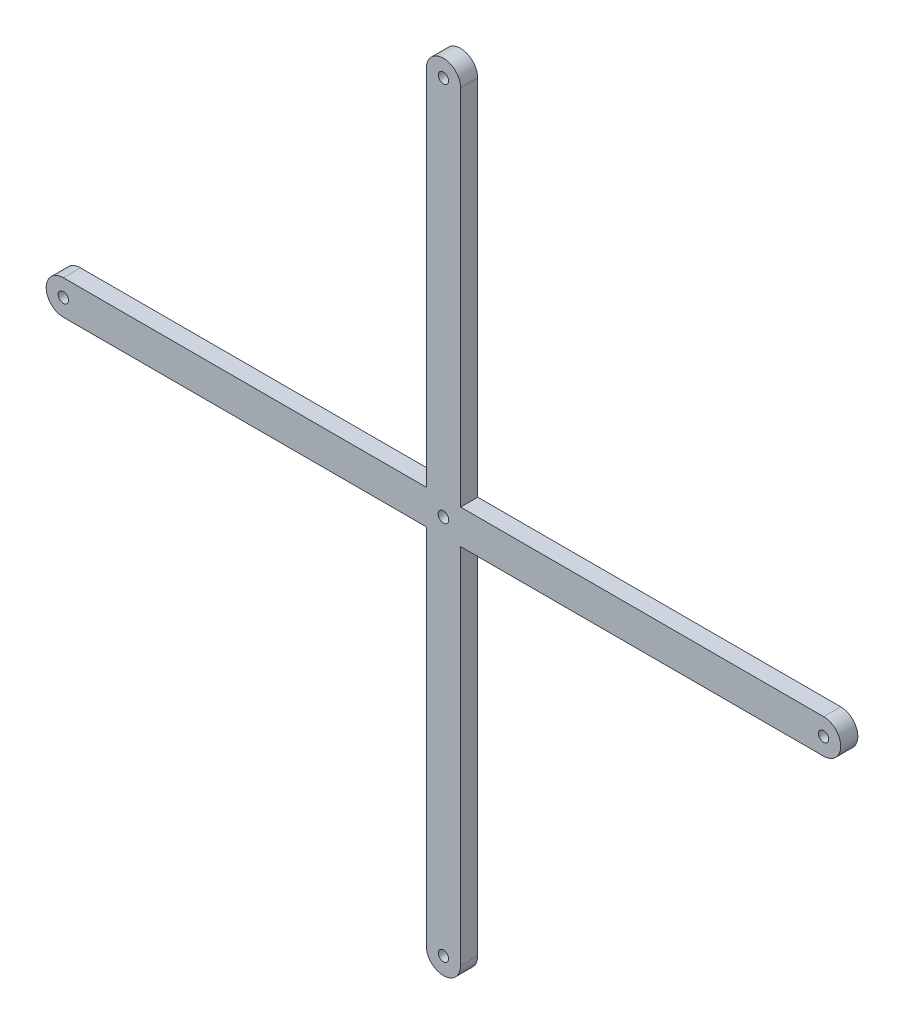
SolidWorks part; units mm, degrees
ref_plane "Front Plane" through (0, 0, 0) normal (0, 0, 1) x (1, 0, 0)
ref_plane "Top Plane" through (0, 0, 0) normal (0, 1, 0) x (1, 0, 0)
ref_plane "Right Plane" through (0, 0, 0) normal (1, 0, 0) x (0, 0, -1)
sketch "Sketch1" plane through (0, 0, 0) normal (0, 0, 1) x (1, 0, 0)
  line L0 (111, 0) -> (-111, 0) construction
  line L1 (5, -5) -> (5, -111)
  line L2 (-5, -5) -> (-5, -111)
  line L3 (0, 111) -> (0, -111) construction
  line L5 (-5, 5) -> (-111, 5)
  line L6 (-5, -5) -> (-111, -5)
  line L7 (5, 5) -> (5, 111)
  line L8 (-5, 5) -> (-5, 111)
  line L9 (5, -5) -> (111, -5)
  line L10 (5, 5) -> (111, 5)
  arc A1 (-5, -111) -> (5, -111) centre (0, -111) ccw
  circle A2 centre (0, 0) radius 1.55
  circle A3 centre (0, -111) radius 1.5
  arc A4 (-111, 5) -> (-111, -5) centre (-111, 0) ccw
  arc A5 (5, 111) -> (-5, 111) centre (0, 111) ccw
  arc A6 (111, -5) -> (111, 5) centre (111, 0) ccw
  circle A7 centre (-111, 0) radius 1.5
  circle A8 centre (0, 111) radius 1.5
  circle A9 centre (111, 0) radius 1.5
  point P3 (0, -55.5)
  point P34 (0, 0)
  point P37 (0, 0)
  dimension "D2" = 4
  dimension "D3" = 3
  dimension "D4" = 3.1
  dimension "D5" = 5
  dimension "D6" = 4
extrude "Boss-Extrude1" add sketch "Sketch1" along normal blind 5
